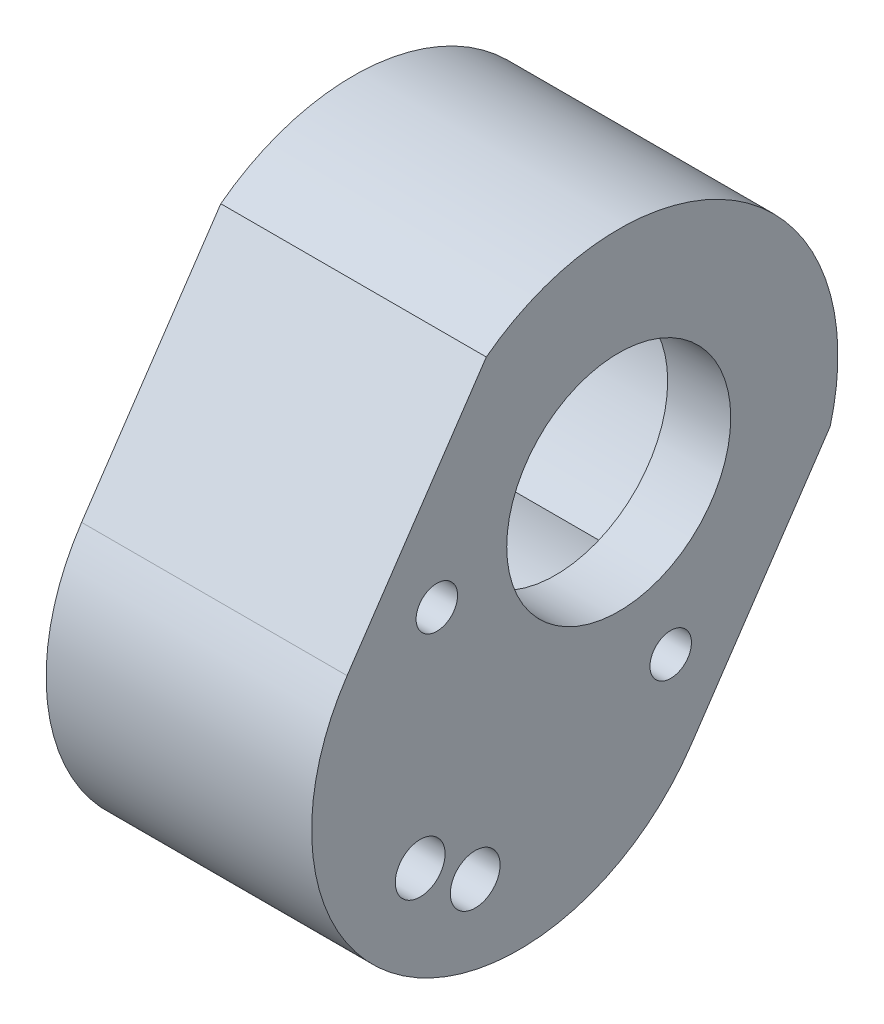
SolidWorks part; units mm, degrees
ref_plane "前视基准面" through (0, 0, 0) normal (0, 0, 1) x (1, 0, 0)
ref_plane "上视基准面" through (0, 0, 0) normal (0, 1, 0) x (1, 0, 0)
ref_plane "右视基准面" through (0, 0, 0) normal (1, 0, 0) x (0, 0, -1)
sketch "草图1" plane through (0, 0, 0) normal (1, 0, 0) x (0, 0, -1)
  line L0 (11.0605, 38.2338) -> (39.8744, 38.2338) construction
  line L1 (14.9756, 21.1312) -> (1.6162, 0)
  line L2 (1.6162, 0) -> (19.8234, 0)
  line L3 (23.5745, 54.705) -> (15.1867, 42.2695)
  line L4 (35.9126, 28.2896) -> (44.3005, 40.7252)
  line L5 (18.5597, 24.9166) -> (38.9397, 55.1311) construction
  line L6 (18.5597, 24.9166) -> (46.0059, 24.9166) construction
  arc A0 (15.1867, 42.2695) -> (35.9126, 28.2896) centre (25.5496, 35.2795) ccw
  arc A1 (23.5745, 54.705) -> (44.3005, 40.7252) centre (31.5548, 44.1826) cw
  arc A2 (20.4616, 46.3345) -> (37.7056, 34.7033) centre (31.5548, 44.1826) cw
  arc A3 (20.4616, 46.3345) -> (37.7056, 34.7033) centre (26.6124, 36.8552) ccw
  circle A4 centre (31.5548, 44.1826) radius 6.75
  dimension "D3" = 56
  dimension "D6" = 11.3
  dimension "D7" = 11.3
  dimension "D8" = 13.5
  dimension "D1" = 15
  dimension "D2" = 15
  dimension "D4" = 25
  dimension "D5" = 2.1
extrude "凸台-拉伸1" add sketch "草图1" along normal blind 16 from offset 1.3 contours A0 L4 A1 L3
extrude "切除-拉伸1" cut sketch "草图1<3>" along normal blind 13.5 contours A3 A2
sketch "草图1<3>" plane through (0, 0, 0) normal (1, 0, 0) x (0, 0, -1) same geometry as "草图1"
extrude "切除-拉伸2" cut sketch "草图1<4>" along normal through all contours A4
sketch "草图1<4>" plane through (0, 0, 0) normal (1, 0, 0) x (0, 0, -1) same geometry as "草图1"
sketch "草图2" plane through (13.5, 0, 0) normal (-1, 0, 0) x (0, 0, 1)
  arc A3 (-20.4616, 46.3345) -> (-37.7056, 34.7033) centre (-31.5548, 44.1826) ccw construction
  arc A4 (-37.7056, 34.7033) -> (-20.4616, 46.3345) centre (-26.6124, 36.8552) ccw construction
  arc A5 (-36.7968, 35.3163) -> (-21.3704, 45.7215) centre (-26.6124, 36.8552) ccw
  arc A6 (-21.3704, 45.7215) -> (-36.7968, 35.3163) centre (-31.5548, 44.1826) ccw
  arc A7 (-36.7968, 35.3163) -> (-21.3704, 45.7215) centre (-26.6124, 36.8552) ccw
  arc A8 (-21.3704, 45.7215) -> (-36.7968, 35.3163) centre (-31.5548, 44.1826) ccw
  arc A9 (-20.4616, 46.3345) -> (-37.7056, 34.7033) centre (-31.5548, 44.1826) ccw
  arc A10 (-37.7056, 34.7033) -> (-20.4616, 46.3345) centre (-26.6124, 36.8552) ccw
  dimension "D1" = 1
extrude "凸台-拉伸2" add sketch "草图2" along normal blind 10
sketch "草图3" plane through (13.5, 0, 0) normal (-1, 0, 0) x (0, 0, 1)
  line L0 (-37.3145, 52.7217) -> (-20.8527, 28.3161) construction
  line L1 (-31.5548, 44.1826) -> (-38.3048, 39.6297) construction
  arc A0 (-21.3704, 45.7215) -> (-36.7968, 35.3163) centre (-31.5548, 44.1826) ccw construction
  arc A1 (-36.7968, 35.3163) -> (-21.3704, 45.7215) centre (-26.6124, 36.8552) ccw construction
  circle A2 centre (-34.6873, 33.6262) radius 1.25
  circle A4 centre (-20.5937, 43.1325) radius 1.25
  circle A5 centre (-22.9057, 27.7832) radius 1.5
  arc A6 (-37.7056, 34.7033) -> (-20.4616, 46.3345) centre (-26.6124, 36.8552) ccw construction
  circle A7 centre (-19.5896, 30.02) radius 1.5
  dimension "D1" = 2.5
  dimension "D3" = 2
  dimension "D4" = 3
  dimension "D2" = 8.5
  dimension "D5" = 7
extrude "切除-拉伸4" cut sketch "草图3" against normal through all and the other way through all
